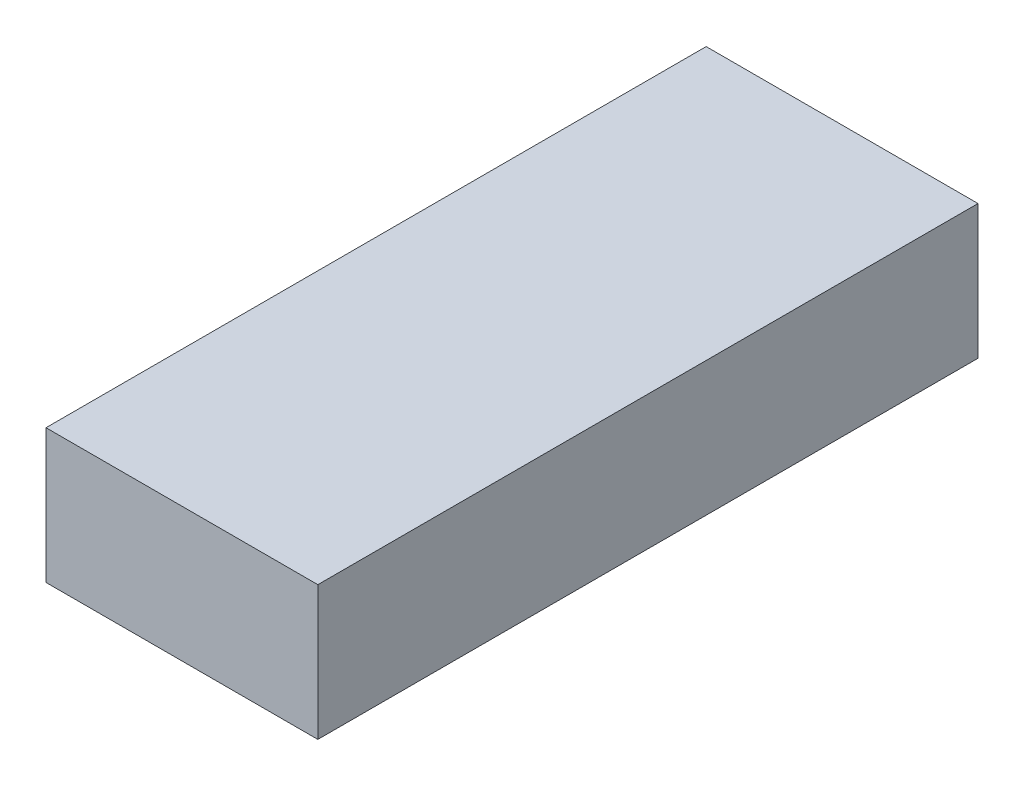
SolidWorks part; units mm, degrees
ref_plane "Front Plane" through (0, 0, 0) normal (0, 0, 1) x (1, 0, 0)
ref_plane "Top Plane" through (0, 0, 0) normal (0, 1, 0) x (1, 0, 0)
ref_plane "Right Plane" through (0, 0, 0) normal (1, 0, 0) x (0, 0, -1)
sketch "Sketch1" plane through (0, 0, 0) normal (0, 1, 0) x (1, 0, 0)
  line L0 (-16.5, 98) -> (-16.5, 1)
  line L1 (-17.5, 99) -> (17.5, 99) construction
  line L2 (-17.5, 99) -> (-17.5, 0) construction
  line L3 (-17.5, 0) -> (17.5, 0) construction
  line L4 (17.5, 99) -> (17.5, 0) construction
  line L5 (-16.5, 1) -> (16.5, 1)
  line L6 (16.5, 98) -> (16.5, 1)
  line L7 (-16.5, 98) -> (16.5, 98)
  line L8 (-17.7, 99.2) -> (-17.7, -0.2)
  line L9 (-17.7, -0.2) -> (17.7, -0.2)
  line L10 (17.7, 99.2) -> (17.7, -0.2)
  line L11 (-17.7, 99.2) -> (17.7, 99.2)
  point P4 (0, 0)
  dimension "D1" = 35
  dimension "D2" = 99
  dimension "D3" = 1
  dimension "D4" = 0.2
extrude "Boss-Extrude1" add sketch "Sketch1" along normal blind 2.4
sketch "Sketch2" plane through (0, 2.4, 0) normal (0, 1, 0) x (1, 0, 0)
  line L0 (-19.7, 101.2) -> (19.7, 101.2)
  line L1 (-17.7, -0.2) -> (17.7, -0.2)
  line L2 (-17.7, -0.2) -> (-17.7, 99.2)
  line L3 (-17.7, 99.2) -> (17.7, 99.2)
  line L4 (17.7, -0.2) -> (17.7, 99.2)
  line L5 (19.7, -2.2) -> (19.7, 101.2)
  line L6 (-19.7, -2.2) -> (19.7, -2.2)
  line L7 (-19.7, -2.2) -> (-19.7, 101.2)
  dimension "D1" = 2
extrude "Boss-Extrude3" add sketch "Sketch2" against normal offset from surface (15.4 mm away) 13 up to face at (0, 0, -49.5) offset beyond the face yes
sketch "Sketch3" plane through (0, 2.4, 0) normal (0, 1, 0) x (1, 0, 0)
  line L1 (-19.7, -2.2) -> (19.7, -2.2)
  line L2 (-19.7, -2.2) -> (-19.7, 101.2)
  line L3 (-19.7, 101.2) -> (19.7, 101.2)
  line L4 (19.7, -2.2) -> (19.7, 101.2)
extrude "Boss-Extrude4" add sketch "Sketch3" along normal blind 2
sketch "Sketch4" plane through (0, 4.4, 0) normal (0, 1, 0) x (1, 0, 0)
  line L0 (21.7, 101.2) -> (21.7, -4.2)
  line L1 (21.7, -4.2) -> (-21.7, -4.2)
  line L2 (-21.7, -4.2) -> (-21.7, 101.2)
  line L3 (-21.7, 101.2) -> (-19.7, 101.2)
  line L4 (19.7, 101.2) -> (21.7, 101.2)
  line L5 (19.7, 101.2) -> (19.7, -2.2)
  line L6 (19.7, -2.2) -> (-19.7, -2.2)
  line L7 (-19.7, -2.2) -> (-19.7, 101.2)
  dimension "D1" = 2
extrude "Boss-Extrude5" add sketch "Sketch4" against normal offset from surface (21.4 mm away) 4 up to face at (0, -13, -49.5) offset beyond the face yes
sketch "Sketch5" plane through (0, -13, 0) normal (0, -1, 0) x (1, 0, 0)
  line L0 (0, -83.2) -> (0, -99.2) construction
  line L1 (-15.2, -23.2) -> (15.2, -23.2) construction
  line L2 (-15.2, -23.2) -> (-15.2, -83.2) construction
  line L3 (-15.2, -83.2) -> (15.2, -83.2) construction
  line L4 (15.2, -23.2) -> (15.2, -83.2) construction
  line L5 (17.7, -99.2) -> (-17.7, -99.2) construction
  line L6 (19.7, -101.2) -> (19.7, 2.2) construction
  line L8 (19.7, -101.2) -> (-19.7, -101.2) construction
  line L10 (-19.7, -101.2) -> (-19.7, 2.2) construction
  circle A0 centre (-15.2, -23.2) radius 5
  circle A1 centre (15.2, -23.2) radius 5
  circle A2 centre (15.2, -83.2) radius 5
  circle A3 centre (-15.2, -83.2) radius 5
  dimension "D1" = 10
  dimension "D2" = 60
  dimension "D3" = 30.4
  dimension "D4" = 18
extrude "Cut-Extrude1" cut sketch "Sketch5" along normal blind 2.4
sketch "Sketch6" plane through (0, -17, 0) normal (0, -1, 0) x (1, 0, 0)
  line L0 (21.7, -101.2) -> (19.7, -101.2) construction
  line L1 (-21.7, 4.2) -> (-17.7, 4.2)
  line L2 (-21.7, 4.2) -> (-21.7, -101.2)
  line L3 (-21.7, -101.2) -> (-17.7, -101.2)
  line L4 (-17.7, 4.2) -> (-17.7, -101.2)
  line L5 (21.7, 4.2) -> (17.7, 4.2)
  line L6 (21.7, 4.2) -> (21.7, -101.2)
  line L7 (21.7, -101.2) -> (17.7, -101.2)
  line L8 (17.7, 4.2) -> (17.7, -101.2)
  line L9 (-17.7, -99.2) -> (-17.7, 0.2) construction
  line L10 (17.7, 0.2) -> (17.7, -99.2) construction
extrude "Boss-Extrude6" add sketch "Sketch6" against normal up to surface (1.6 mm away) up to face at (-19.95, -15.4, -83.2)
chamfer "Chamfer1" distance 0.4 distance2 2 2 edges at (17.7, -15.4, -49.5) (-17.7, -15.4, -49.5) first distance on face at (17.7, -16.2, -49.5) first distance on face at (-17.7, -16.2, -49.5)
